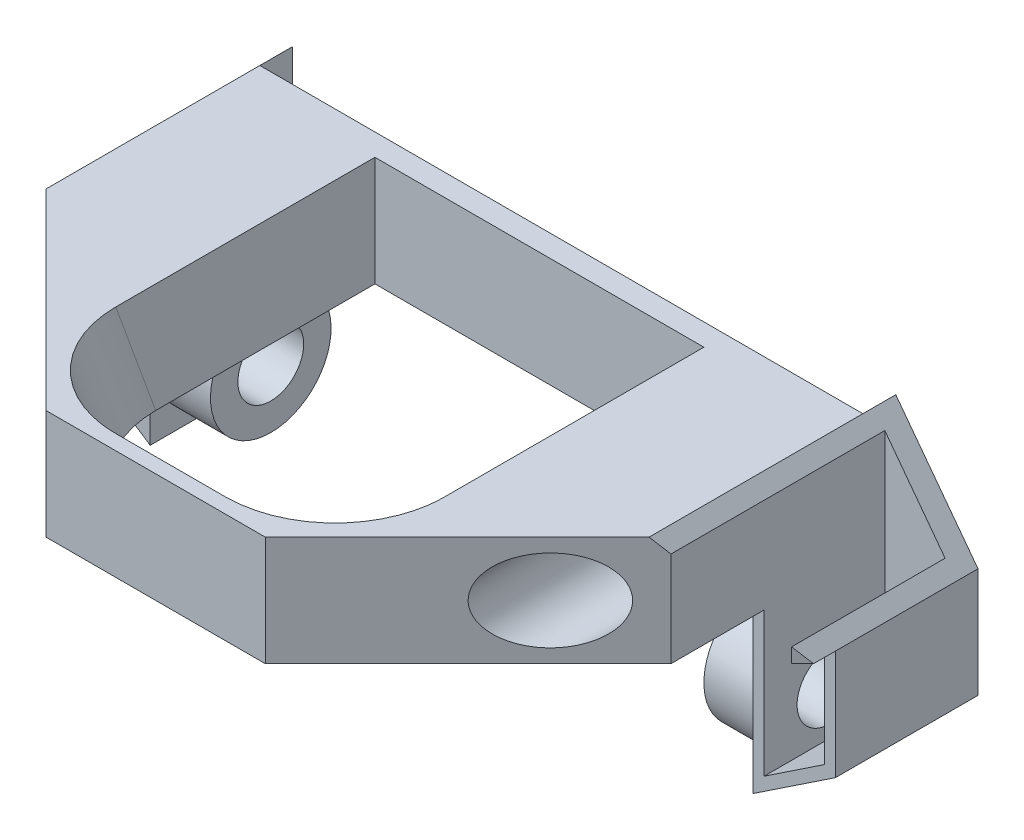
SolidWorks part; units mm, degrees
ref_plane "Front Plane" through (0, 0, 0) normal (0, 0, 1) x (1, 0, 0)
ref_plane "Top Plane" through (0, 0, 0) normal (0, 1, 0) x (1, 0, 0)
ref_plane "Right Plane" through (0, 0, 0) normal (1, 0, 0) x (0, 0, -1)
sketch "Sketch1" plane through (0, 0, 0) normal (0, 0, 1) x (1, 0, 0)
  line L0 (-27.5, 0) -> (27.5, 0)
  line L1 (27.5, 0) -> (27.5, -15)
  line L2 (27.5, -15) -> (35, -10)
  line L3 (35, -10) -> (35, 0)
  line L4 (35, 0) -> (27.5, 10)
  line L5 (27.5, 10) -> (-27.5, 10)
  line L6 (-27.5, 10) -> (-35, 0)
  line L7 (-35, 0) -> (-35, -10)
  line L8 (-35, -10) -> (-27.5, -15)
  line L9 (-27.5, -15) -> (-27.5, 0)
  line L10 (-27.5, 10) -> (-27.5, 0) construction
  line L11 (27.5, 10) -> (27.5, 0) construction
  line L12 (35, 0) -> (27.5, 0) construction
  line L13 (-27.5, 0) -> (-35, 0) construction
  line L14 (-27.5, -15) -> (27.5, -15) construction
  line L15 (-35, -10) -> (35, -10) construction
  dimension "D1" = 70
  dimension "D2" = 55
  dimension "D3" = 15
  dimension "D4" = 10
  dimension "D5" = 10
extrude "Boss-Extrude1" add sketch "Sketch1" along normal blind 40
chamfer "Chamfer1" distance 25 angle 45 2 edges at (35, -5, 40) (-35, -5, 40)
sketch "Sketch3" plane through (0, 0, 0) normal (0, 0, -1) x (-1, 0, 0)
  line L1 (-27.5, -15.4249) -> (27.5, -15.4249)
  line L2 (-27.5, -15.4249) -> (-27.5, 15.4249)
  line L3 (-27.5, 15.4249) -> (27.5, 15.4249)
  line L4 (27.5, -15.4249) -> (27.5, 15.4249)
  line L5 (-27.5, -15.4249) -> (27.5, 15.4249) construction
  line L6 (-27.5, 15.4249) -> (27.5, -15.4249) construction
  point P0 (0, 0)
  dimension "D1" = 55
extrude "Cut-Extrude2" cut sketch "Sketch3" against normal blind 3
sketch "Sketch5" plane through (0, 0, 0) normal (0, 0, -1) x (-1, 0, 0)
  line L0 (-23, 5) -> (23, 5) construction
  line L1 (0, 5) -> (0, 0) construction
  circle A0 centre (-23, 5) radius 1.75
  circle A1 centre (23, 5) radius 1.75
  dimension "D1" = 3.5
  dimension "D2" = 46
  dimension "D3" = 5
extrude "Cut-Extrude4" cut sketch "Sketch5" against normal through all
sketch "Sketch4" plane through (0, 0, 40) normal (0, 0, 1) x (1, 0, 0)
  line L3 (-35, 0) -> (-27.5, 10) construction
  line L4 (-34, 1.3333) -> (-28.5, 8.6667)
  line L6 (-34, -9.4648) -> (-34, 0)
  line L7 (-28.5, -13.1315) -> (-34, -9.4648)
  line L8 (-28.5, 0) -> (-28.5, -13.1315)
  line L9 (-34, -9.4648) -> (-34, 1.3333)
  line L10 (-28.5, -13.1315) -> (-34, -9.4648)
  line L11 (-28.5, 8.6667) -> (-28.5, -13.1315)
  dimension "D1" = 1
extrude "Cut-Extrude3" cut sketch "Sketch4" against normal blind 38
sketch "Sketch6" plane through (-27.5, 0, 0) normal (1, 0, 0) x (0, 0, -1)
  line L0 (0, -15) -> (0, 10) construction
  line L1 (-22.5, -15) -> (0, -15) construction
  circle A0 centre (-7, -9) radius 3
  circle A1 centre (-7, -9) radius 5.5
  dimension "D3" = 6
  dimension "D1" = 7
  dimension "D2" = 6
  dimension "D4" = 2.5
extrude "Boss-Extrude2" add sketch "Sketch6" along normal blind 5
sketch "Sketch7" plane through (-27.5, 0, 0) normal (1, 0, 0) x (0, 0, -1)
  circle A1 centre (-7, -9) radius 3
  circle A2 centre (-7, -9) radius 3
  dimension "D1" = 0
extrude "Cut-Extrude5" cut sketch "Sketch7" against normal blind 2
mirror "Mirror1" about plane through (0, 0, 0) normal (1, 0, 0) of "Cut-Extrude5", "Boss-Extrude2", "Cut-Extrude3"
sketch "Sketch9" plane through (0, 0, 40) normal (0, 0, 1) x (1, 0, 0)
  circle A10 centre (-23, 5) radius 3.75
  circle A11 centre (-23, 5) radius 3.75
  circle A13 centre (23, 5) radius 3.75
  circle A14 centre (23, 5) radius 3.75
  dimension "D1" = 2
  dimension "D2" = 2
extrude "Cut-Extrude7" cut sketch "Sketch9" against normal blind 24
sketch "Sketch10" plane through (0, 0, 40) normal (0, 0, 1) x (1, 0, 0)
  line L1 (-38.1959, 0) -> (41.8615, 0)
  line L2 (-38.1959, 0) -> (-38.1959, -23.2108)
  line L3 (-38.1959, -23.2108) -> (41.8615, -23.2108)
  line L4 (41.8615, 0) -> (41.8615, -23.2108)
extrude "Cut-Extrude8" cut sketch "Sketch10" against normal blind 27
sketch "Sketch2" plane through (0, 0, 0) normal (0, -1, 0) x (1, 0, 0)
  line L0 (-27.5, 0) -> (27.5, 0) construction
  line L1 (-15, -35) -> (15, -35)
  line L2 (-15, -35) -> (-15, 25)
  line L3 (-5, 35) -> (5, 35)
  line L4 (15, -35) -> (15, 25)
  line L5 (-15, -35) -> (15, 35) construction
  line L6 (-15, 35) -> (15, -35) construction
  arc A0 (5, 35) -> (15, 25) centre (5, 25) cw
  arc A1 (-15, 25) -> (-5, 35) centre (-5, 25) cw
  point P0 (0, 0)
  dimension "D3" = 10
  dimension "D1" = 30
  dimension "D2" = 35
sketch "Sketch11" plane through (0, 0, 0) normal (1, 0, 0) x (0, 0, -1)
  line L0 (0, 0) -> (-9.227, 25.3509)
  line L1 (0, 0) -> (0, 10) construction
  dimension "D1" = 20
sweep "Cut-Sweep1" cut profiles "Sketch2" path "Sketch11"
sketch "Sketch13" plane through (0, 0, 0) normal (0, -1, 0) x (1, 0, 0)
  line L0 (-27.5, 22.5) -> (-27.5, 3) construction
  line L1 (-27.5, 11) -> (-22.5, 11)
  line L2 (-27.5, 11) -> (-27.5, 3)
  line L3 (-27.5, 3) -> (-22.5, 3)
  line L4 (-22.5, 11) -> (-22.5, 3)
  line L6 (-27.5, 3) -> (-15, 3) construction
  point P6 (-25.0717, 4)
  dimension "D1" = 5
  dimension "D2" = 8
extrude "Boss-Extrude3" add sketch "Sketch13" along normal up to next
sketch "Sketch14" plane through (0, 0, 40) normal (0, 0, 1) x (1, 0, 0)
  line L1 (-34, -9.4648) -> (-42.3014, -9.4648)
  line L2 (-34, -9.4648) -> (-34, 7.947)
  line L3 (-34, 7.947) -> (-42.3014, 7.947)
  line L4 (-42.3014, -9.4648) -> (-42.3014, 7.947)
extrude "Cut-Extrude9" cut sketch "Sketch14" against normal blind 38
sketch "Sketch15" plane through (0, 10, 0) normal (0, 1, 0) x (1, 0, 0)
  line L0 (15, -28.6397) -> (15, -3) construction
  line L1 (-15, -3) -> (15, -3)
  line L2 (-15, -3) -> (-15, -5)
  line L3 (-15, -5) -> (15, -5)
  line L4 (15, -3) -> (15, -5)
  dimension "D1" = 2
extrude "Boss-Extrude4" add sketch "Sketch15" against normal up to surface (10 mm away) up to face at (-2.5, 0, 18.5079)
